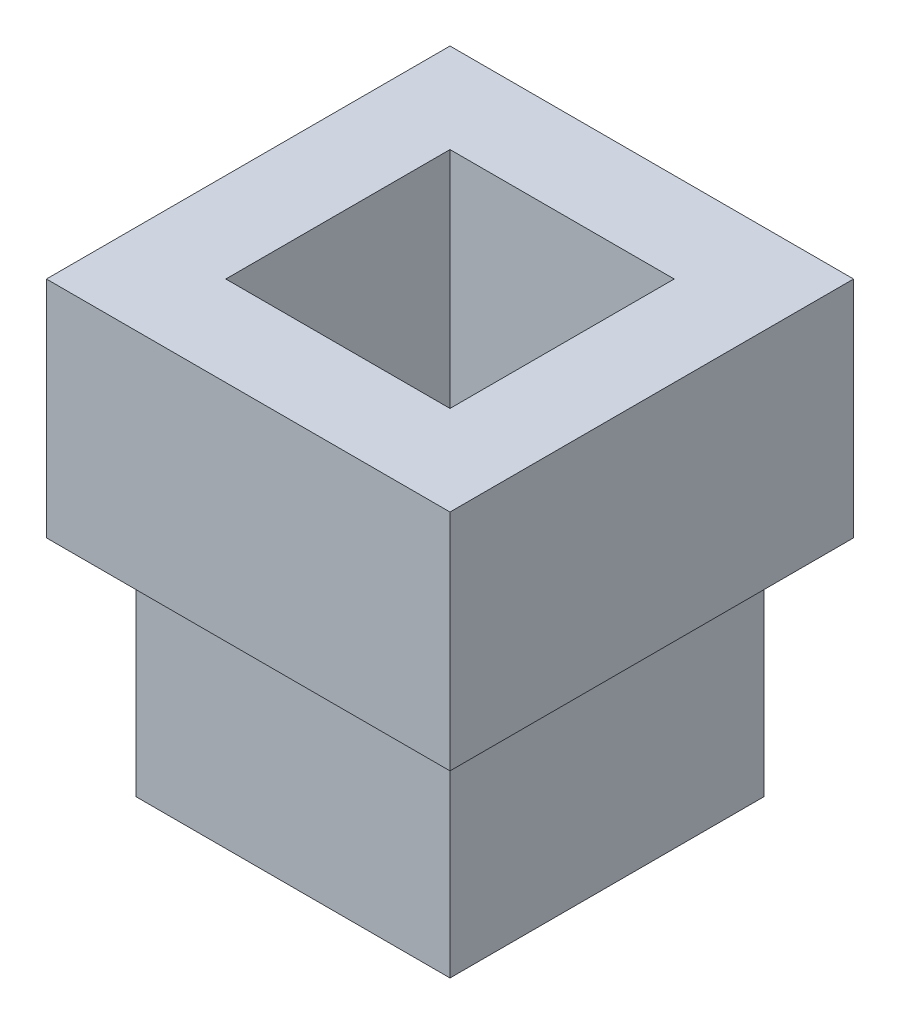
SolidWorks part; units mm, degrees
material "Delrin 2700 NC010, Low Viscosity Acetal Copolymer (SS)"
ref_plane "Front" through (0, 0, 0) normal (0, 0, 1) x (1, 0, 0)
ref_plane "Top" through (0, 0, 0) normal (0, 1, 0) x (1, 0, 0)
ref_plane "Right" through (0, 0, 0) normal (1, 0, 0) x (0, 0, -1)
sketch "Sketch1" plane through (0, 0, 0) normal (0, 1, 0) x (1, 0, 0)
  line L0 (17.5, -17.5) -> (17.5, 17.5)
  line L1 (-22.5, -22.5) -> (22.5, -22.5)
  line L2 (-22.5, -22.5) -> (-22.5, 22.5)
  line L3 (-22.5, 22.5) -> (22.5, 22.5)
  line L4 (22.5, -22.5) -> (22.5, 22.5)
  line L5 (-22.5, -22.5) -> (22.5, 22.5) construction
  line L6 (-22.5, 22.5) -> (22.5, -22.5) construction
  line L7 (-12.5, -12.5) -> (12.5, -12.5)
  line L8 (-12.5, -12.5) -> (-12.5, 12.5)
  line L9 (-12.5, 12.5) -> (12.5, 12.5)
  line L10 (12.5, -12.5) -> (12.5, 12.5)
  line L11 (-12.5, -12.5) -> (12.5, 12.5) construction
  line L12 (-12.5, 12.5) -> (12.5, -12.5) construction
  line L13 (-17.5, 17.5) -> (17.5, 17.5)
  line L14 (-17.5, -17.5) -> (-17.5, 17.5)
  line L15 (-17.5, -17.5) -> (17.5, -17.5)
  point P0 (0, 0)
  point P6 (0, 0)
  dimension "D1" = 45
  dimension "D2" = 10
  dimension "D3" = 5
extrude "Boss-Extrude1" add sketch "Sketch1" along normal blind 25 contours L14 L15 L0 L13 L10 L7 L8 L9 | L1 L4 L3 L2 L15 L14 L13 L0 region at (0, 0, 17.005) region at (-21.8636, 0, 0)
extrude "Boss-Extrude2" add sketch "Sketch1<3>" against normal blind 25 contours L14 L15 L0 L13 L10 L7 L8 L9 region at (0, 0, 17.005)
sketch "Sketch1<3>" plane through (0, 0, 0) normal (0, 1, 0) x (1, 0, 0) same geometry as "Sketch1"
